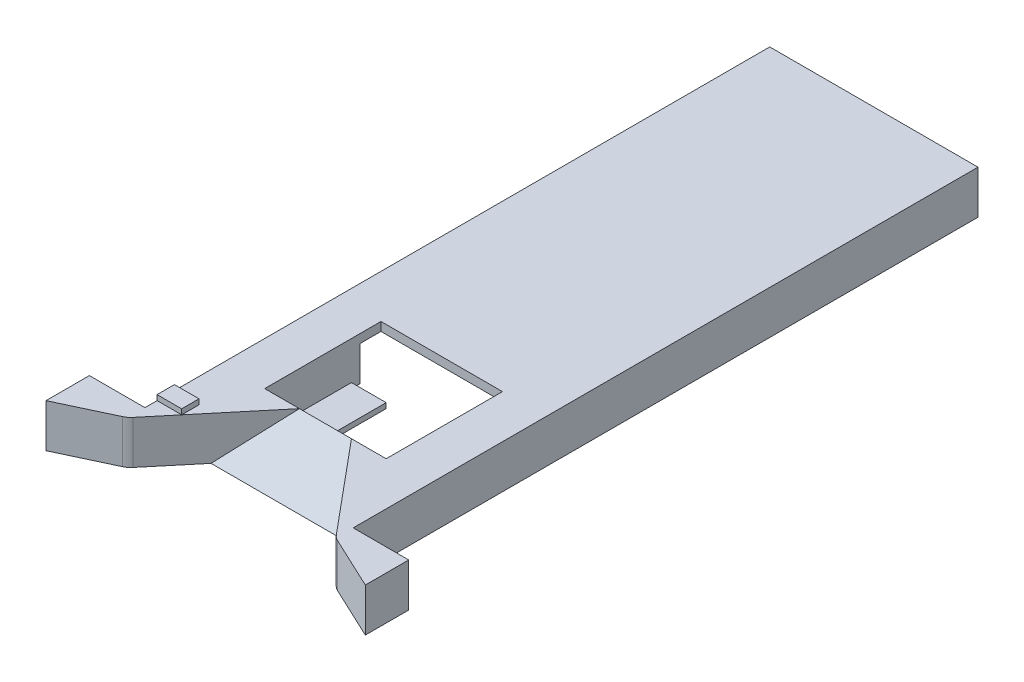
SolidWorks part; units mm, degrees
ref_plane "Front Plane" through (0, 0, 0) normal (0, 0, 1) x (1, 0, 0)
ref_plane "Top Plane" through (0, 0, 0) normal (0, 1, 0) x (1, 0, 0)
ref_plane "Right Plane" through (0, 0, 0) normal (1, 0, 0) x (0, 0, -1)
sketch "Sketch1" plane through (0, 0, 0) normal (0, 1, 0) x (1, 0, 0)
  line L0 (-55, -30) -> (25, -30)
  line L1 (25, -30) -> (0, 0)
  line L2 (0, 0) -> (-30, 0)
  line L3 (-30, 0) -> (-55, -30)
  line L4 (-15, 0) -> (-15, -30)
  dimension "D1" = 30
  dimension "D2" = 80
  dimension "D3" = 30
  dimension "D4" = 90
extrude "Boss-Extrude1" add sketch "Sketch1" along normal blind 27 contours L4 L2 L3 L0 | L2 L4 L0 L1 region at (-29.697, 0, 17.2727) region at (-0.303, 0, 17.2727)
sketch "Sketch3" plane through (0, 0, 0) normal (1, 0, 0) x (0, 0, -1)
  line L0 (-30, 0) -> (0, 27)
  line L1 (-30, 0) -> (-30, 27)
  line L2 (-30, 27) -> (0, 27)
extrude "Cut-Extrude1" cut sketch "Sketch3" against normal blind 70 and the other way blind 29
sketch "Sketch5" plane through (0, 0, 0) normal (0, 1, 0) x (1, 0, 0)
  line L0 (-55, -30) -> (-75, -54)
  line L1 (-75, -54) -> (-75, 316)
  line L2 (-75, 316) -> (45, 316)
  line L3 (45, 316) -> (45, -54)
  line L4 (45, -54) -> (25, -30)
  line L9 (-55, -30) -> (25, -30)
  line L10 (-30, 0) -> (-55, -30)
  line L11 (0, 0) -> (-30, 0)
  line L12 (25, -30) -> (0, 0)
  line L14 (-30, 0) -> (-55, -30)
  line L15 (0, 0) -> (-30, 0)
  line L16 (25, -30) -> (0, 0)
  dimension "D1" = 120
  dimension "D3" = 370
  dimension "D4" = 370
  dimension "D6" = 0
extrude "Boss-Extrude2" add sketch "Sketch5" along normal up to vertex (27 mm away) up to point (-30, 27, 0)
sketch "Sketch6" plane through (-75, 0, 0) normal (-1, 0, 0) x (0, 0, 1)
  line L0 (-316, 20) -> (34.666, 20)
  line L1 (-316, 27) -> (-316, 0) construction
  line L2 (34.666, 20) -> (34.666, 0)
  line L3 (-316, 0) -> (54, 0) construction
  line L4 (34.666, 0) -> (-316, 0)
  line L5 (-316, 0) -> (-316, 20)
  line L6 (-316, 27) -> (54, 27) construction
  line L7 (54, 27) -> (54, 0) construction
  dimension "D1" = 7
  dimension "D2" = 19.334
sketch "Sketch9" plane through (0, 27, 0) normal (0, 1, 0) x (1, 0, 0)
  line L1 (35, -42) -> (45, -42)
  line L2 (35, -42) -> (35, -27)
  line L3 (35, -27) -> (45, -27)
  line L4 (45, -42) -> (45, -27)
  line L5 (0, 0) -> (45, -54) construction
  line L6 (45, -54) -> (45, 316) construction
  line L8 (-75, -54) -> (-30, 0) construction
  line L9 (-60.8333, -37) -> (-60.8333, -27)
  line L10 (-60.8333, -27) -> (-75, -27)
  line L11 (-75, 316) -> (-75, -54) construction
  line L12 (-75, -27) -> (-75, -37)
  line L13 (-75, -37) -> (-60.8333, -37)
  line M8 (-75, 316) -> (-75, -54)
  dimension "D1" = 10
  dimension "D2" = 15
  dimension "D3" = 10
extrude "Boss-Extrude3" add sketch "Sketch9" along normal blind 3 contours L13 L9 L10 M8 region at (-67.9167, 27, 32)
sketch "Sketch10" plane through (0, 27, 0) normal (0, 1, 0) x (1, 0, 0)
  line L1 (-30, 0) -> (0, 0)
  line L2 (-30, 0) -> (-30, 50)
  line L3 (-30, 50) -> (0, 50)
  line L4 (0, 0) -> (0, 50)
  dimension "D1" = 50
  dimension "D2" = 30
extrude "Cut-Extrude7" cut sketch "Sketch10" against normal through all
sketch "Sketch11" plane through (0, 27, 0) normal (0, 1, 0) x (1, 0, 0)
  line L0 (-30, 50) -> (-30, 0) construction
  line L5 (-30, 0) -> (-50, 0)
  line L6 (-30, 0) -> (-30, 50)
  line L7 (-30, 50) -> (-50, 50)
  line L8 (-50, 0) -> (-50, 50)
  dimension "D5" = 50
  dimension "D6" = 20
extrude "Cut-Extrude9" cut sketch "Sketch11" against normal offset from surface (22 mm away) 5 up to face at (-15, 0, -25)
sketch "Sketch16" plane through (0, 27, 0) normal (0, 1, 0) x (1, 0, 0)
  line L0 (-75, -54) -> (-107, -69)
  line L1 (-107, -69) -> (-107, -54)
  line L5 (-107, -54) -> (-107, -44)
  line L6 (-107, -44) -> (-75, -44)
  line L7 (-75, -34.666) -> (-75, 316) construction
  line L8 (-75, -44) -> (-75, -54)
  line L9 (-75, -37) -> (-75, -54) construction
  dimension "D1" = 32
  dimension "D2" = 15
  dimension "D3" = 10
extrude "Boss-Extrude4" add sketch "Sketch16" against normal up to surface (27 mm away) up to face at (-15, 0, -25)
ref_plane "Plane2" through (-15, 0, 0) normal (-1, 0, 0) x (0, 0, 1)
mirror "Mirror1" about plane through (-15, 0, 0) normal (-1, 0, 0) of "Boss-Extrude4"
fillet "Fillet1" radius 10 1 edges at (-75, 13.5, 54)
fillet "Fillet2" radius 10 1 edges at (45, 13.5, 54)
sketch "Sketch17" plane through (77, 0, 0) normal (1, 0, 0) x (0, 0, -1)
  line L0 (-69, 2) -> (-69, 0)
  line L1 (-69, 0) -> (-69, 27) construction
  line L2 (-69, 0) -> (316, 0)
  line L3 (316, 0) -> (316, 2)
  line L4 (316, 0) -> (316, 20) construction
  line L5 (316, 2) -> (-69, 2)
  dimension "D1" = 2
extrude "Cut-Extrude10" cut sketch "Sketch17" against normal through all and the other way through all
sketch "Sketch18" plane through (0, 27, 0) normal (0, 1, 0) x (1, 0, 0)
  line L5 (20, 0) -> (0, 0)
  line L6 (20, 0) -> (20, 50)
  line L7 (20, 50) -> (0, 50)
  line L8 (0, 0) -> (0, 50)
  dimension "D5" = 50
  dimension "D6" = 20
extrude "Cut-Extrude11" cut sketch "Sketch18" against normal offset from surface (22 mm away) 3 up to face at (-15, 2, -3.3997)
shell "Shell1" thickness 5 removed face at (-15, 2, -3.3997)
sketch "Sketch20" plane through (0, 27, 0) normal (0, 1, 0) x (1, 0, 0)
  line L0 (-50, 50) -> (-50, 67)
  line L1 (-50, 67) -> (20, 67)
  line L2 (20, 67) -> (20, 50)
  line L3 (20, 50) -> (-50, 50)
  line L4 (-50, 50) -> (-50, 0) construction
  line L9 (20, 0) -> (20, 50) construction
  line L11 (45, -44) -> (77, -44) construction
  dimension "D1" = 17
  dimension "D2" = 94
extrude "Cut-Extrude12" cut sketch "Sketch20" against normal through all both and the other way through all
